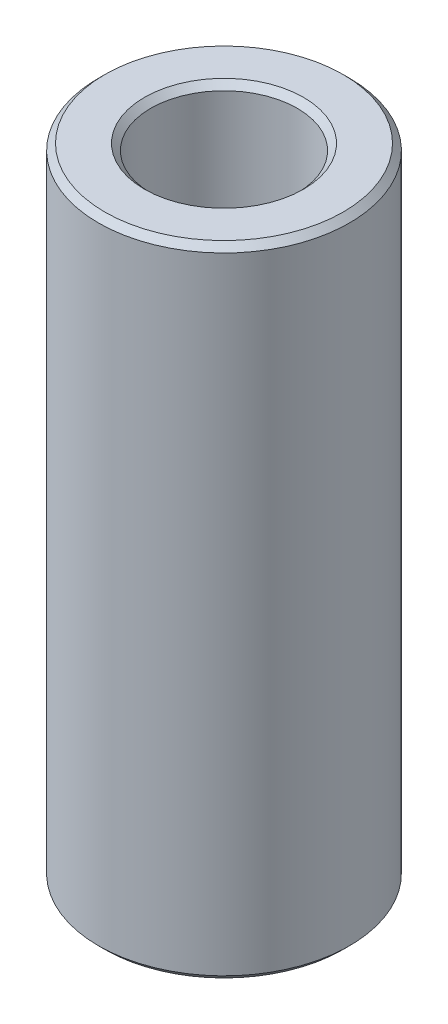
SolidWorks part; units mm, degrees
ref_plane "Front Plane" through (0, 0, 0) normal (0, 0, 1) x (1, 0, 0)
ref_plane "Top Plane" through (0, 0, 0) normal (0, 1, 0) x (1, 0, 0)
ref_plane "Right Plane" through (0, 0, 0) normal (1, 0, 0) x (0, 0, -1)
sketch "Sketch1" plane through (0, 0, 0) normal (0, 1, 0) x (1, 0, 0)
  circle A0 centre (0, 0) radius 37.5
  dimension "SLEEVE_OD" = 75
extrude "Boss-Extrude1" add sketch "Sketch1" along normal blind 190.8737
sketch "Sketch2" plane through (0, 0, 0) normal (0, 1, 0) x (1, 0, 0)
  circle A0 centre (0, 0) radius 21.901
  dimension "BORE_D" = 43.8021
extrude "Cut-Extrude1" cut sketch "Sketch2" along normal through all
chamfer "Chamfer1" distance 1.8849 angle 45 4 edges at (0, 190.8737, 21.901) (0, 0, 21.901) (0, 0, 37.5) (0, 190.8737, 37.5)
